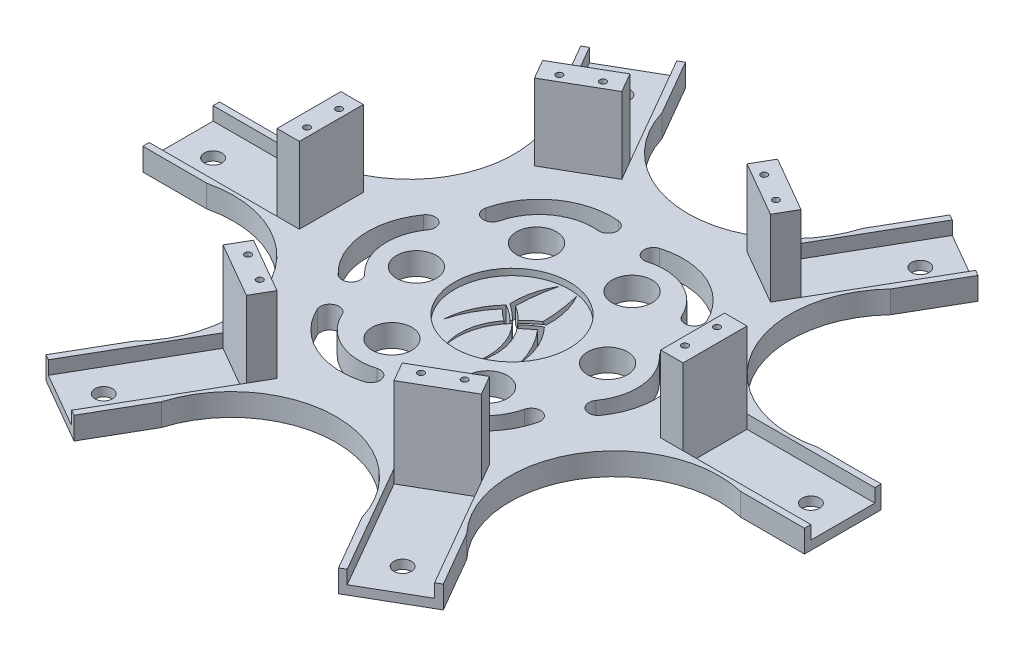
SolidWorks part; units mm, degrees
ref_plane "Front Plane" through (0, 0, 0) normal (0, 0, 1) x (1, 0, 0)
ref_plane "Top Plane" through (0, 0, 0) normal (0, 1, 0) x (1, 0, 0)
ref_plane "Right Plane" through (0, 0, 0) normal (1, 0, 0) x (0, 0, -1)
sketch "Sketch1" plane through (0, 0, 0) normal (0, 1, 0) x (1, 0, 0)
  line L0 (62.1466, -83.641) -> (41.362, -95.641)
  line L7 (103.5085, 12) -> (63.5085, 12)
  line L8 (103.5085, 12) -> (103.5085, -12)
  line L9 (103.5085, -12) -> (63.5085, -12)
  line L10 (63.5085, 12) -> (63.5085, -12)
  line L11 (103.5085, 12) -> (63.5085, -12) construction
  line L12 (103.5085, -12) -> (63.5085, 12) construction
  line L13 (62.1466, -83.641) -> (42.1466, -49)
  line L14 (42.1466, -49) -> (21.362, -61)
  line L15 (41.362, -95.641) -> (21.362, -61)
  line L16 (-41.362, -95.641) -> (-62.1466, -83.641)
  line L17 (-41.362, -95.641) -> (-21.362, -61)
  line L18 (-21.362, -61) -> (-42.1466, -49)
  line L19 (-62.1466, -83.641) -> (-42.1466, -49)
  line L20 (-103.5085, -12) -> (-103.5085, 12)
  line L21 (-103.5085, -12) -> (-63.5085, -12)
  line L22 (-63.5085, -12) -> (-63.5085, 12)
  line L23 (-103.5085, 12) -> (-63.5085, 12)
  line L24 (-62.1466, 83.641) -> (-41.362, 95.641)
  line L25 (-62.1466, 83.641) -> (-42.1466, 49)
  line L26 (-42.1466, 49) -> (-21.362, 61)
  line L27 (-41.362, 95.641) -> (-21.362, 61)
  line L28 (41.362, 95.641) -> (62.1466, 83.641)
  line L29 (41.362, 95.641) -> (21.362, 61)
  line L30 (21.362, 61) -> (42.1466, 49)
  line L31 (62.1466, 83.641) -> (42.1466, 49)
  arc A1 (52.1466, 66.3205) -> (83.5085, 12) centre (75.9923, 43.8742) ccw
  arc A2 (83.5085, -12) -> (52.1466, -66.3205) centre (75.9923, -43.8742) ccw
  arc A3 (31.362, -78.3205) -> (-31.362, -78.3205) centre (0, -87.7484) ccw
  arc A4 (-52.1466, -66.3205) -> (-83.5085, -12) centre (-75.9923, -43.8742) ccw
  arc A5 (-83.5085, 12) -> (-52.1466, 66.3205) centre (-75.9923, 43.8742) ccw
  arc A6 (-31.362, 78.3205) -> (31.362, 78.3205) centre (0, 87.7484) ccw
  point P1 (83.5085, 0)
  point P36 (0, 0)
  point P55 (0, 0)
  dimension "D3" = 24
  dimension "D5" = 40
  dimension "D7" = 6
  dimension "D8" = 6
extrude "Boss-Extrude2" add sketch "Sketch1" along normal blind 10 contours A6 L27 L26 L25 A5 L23 L22 L21 A4 L19 L18 L17 A3 L15 L14 L13 A2 L9 L10 L7 A1 L31 L30 L29 | A6 L27 L24 L25 A5 L26 | A6 L29 L30 L31 A1 L28 | A5 L23 L20 L21 A4 L22 | A4 L19 L16 L17 A3 L18 | A3 L15 L0 L13 A2 L14 | A2 L9 L8 L7 A1 L10 region at (41.8243, 0, 72.4419) region at (0, 0, 0) region at (83.6486, 0, 0) region at (-41.8243, 0, 72.4419) region at (41.8243, 0, -72.4419) region at (-83.6486, 0, 0) region at (-41.8243, 0, -72.4419)
sketch "Sketch2" plane through (0, 0, 0) normal (0, -1, 0) x (1, 0, 0)
  line L0 (103.5085, -12) -> (103.5085, 12) construction
  line L1 (73.5085, 15) -> (103.5085, 15)
  line L2 (73.5085, 15) -> (73.5085, -15)
  line L3 (73.5085, -15) -> (103.5085, -15)
  line L4 (103.5085, 15) -> (103.5085, -15)
  line L5 (73.5085, 15) -> (103.5085, -15) construction
  line L6 (73.5085, -15) -> (103.5085, 15) construction
  point P0 (88.5085, 0)
  dimension "D1" = 30
  dimension "D2" = 30
  dimension "D3" = 0
extrude "Cut-Extrude1" cut sketch "Sketch2" against normal blind 3
sketch "Sketch3" plane through (0, 3, 0) normal (0, -1, 0) x (1, 0, 0)
  line L0 (103.5085, -12) -> (103.5085, 12) construction
  circle A0 centre (93.5085, 0) radius 2.75
  dimension "D1" = 5.5
  dimension "D2" = 10
extrude "Boss-Extrude3" add sketch "Sketch3" along normal blind 3
sketch "Sketch4" plane through (103.5085, 0, 0) normal (1, 0, 0) x (0, 0, -1)
  line L0 (-2.75, 3) -> (2.75, 3) construction
  line L1 (-10, 11.5957) -> (10, 11.5957)
  line L2 (-10, 11.5957) -> (-10, 5.8)
  line L3 (-10, 5.8) -> (10, 5.8)
  line L4 (10, 11.5957) -> (10, 5.8)
  line L5 (-10, 11.5957) -> (10, 5.8) construction
  line L6 (-10, 5.8) -> (10, 11.5957) construction
  point P0 (0, 8.6979)
  dimension "D1" = 20
  dimension "D2" = 2.8
  dimension "D3" = 0
extrude "Cut-Extrude2" cut sketch "Sketch4" against normal blind 40
sketch "Sketch5" plane through (0, 10, 0) normal (0, 1, 0) x (1, 0, 0)
  line L1 (56.5085, 10) -> (63.5085, 10)
  line L2 (56.5085, 10) -> (56.5085, -10)
  line L3 (56.5085, -10) -> (63.5085, -10)
  line L4 (63.5085, 10) -> (63.5085, -10)
  line L5 (56.5085, 10) -> (63.5085, -10) construction
  line L6 (56.5085, -10) -> (63.5085, 10) construction
  circle A0 centre (59.1085, 5) radius 1
  circle A1 centre (59.1085, -5) radius 1
  point P0 (60.0085, 0)
  dimension "D2" = 2
  dimension "D1" = 7
  dimension "D3" = 0
  dimension "D4" = 2.6
  dimension "D5" = 10
  dimension "D6" = 5
extrude "Boss-Extrude5" add sketch "Sketch5" along normal blind 23.8
sketch "Sketch7" plane through (0, 10, 0) normal (0, 1, 0) x (1, 0, 0)
  circle A0 centre (0, 0) radius 17.9565
extrude "Cut-Extrude3" cut sketch "Sketch7" against normal blind 2
pattern_circular "CirPattern1" count 6 over 360 about axis through (0, 10, 0) along (0, 1, 0) of "Cut-Extrude1", "Cut-Extrude2", "Boss-Extrude5", "Boss-Extrude3"
sketch "Sketch9" plane through (0, 10, 0) normal (0, 1, 0) x (1, 0, 0)
  arc A0 (-38.6212, 11.6598) -> (-36.1578, -14.0999) centre (-22.6064, 0.1937) ccw construction
  arc A1 (-40.9975, 13.3612) -> (-38.1686, -16.2209) centre (-22.6064, 0.1937) ccw
  arc A2 (-36.2448, 9.9584) -> (-34.147, -11.979) centre (-22.6064, 0.1937) ccw
  arc A3 (-36.2448, 9.9584) -> (-40.9975, 13.3612) centre (-38.6212, 11.6598) ccw
  arc A4 (-38.1686, -16.2209) -> (-34.147, -11.979) centre (-36.1578, -14.0999) ccw
  point P3 (-42.2133, -1.6813)
extrude "Cut-Extrude4" cut sketch "Sketch9" against normal blind 10 contours A2 A4 A1 A3
pattern_circular "CirPattern2" count 6 over 360 about axis through (0, 8, 0) along (0, 1, 0) of "Cut-Extrude4"
sketch "Sketch10" plane through (0, 10, 0) normal (0, 1, 0) x (1, 0, 0)
  line L0 (-21.862, 32.5703) -> (0, 0) construction
  arc A0 (-9.4982, 36.3682) -> (-27.4476, 23.5827) centre (-11.1355, 19.6746) ccw construction
  circle A1 centre (-15.6448, 23.3079) radius 6.2284
extrude "Cut-Extrude5" cut sketch "Sketch10" against normal blind 10
pattern_circular "CirPattern3" count 6 over 360 about axis through (0, 8, 0) along (0, 1, 0) of "Cut-Extrude5"
sketch "Sketch11" plane through (0, 0, 0) normal (0, -1, 0) x (1, 0, 0)
  circle A0 centre (0, 0) radius 76.7132
extrude "Cut-Extrude6" cut sketch "Sketch11" against normal up to surface (3 mm away) up to face at (-44.3727, 3, 82.3558)
extrude "Cut-Extrude14" cut sketch "Sketch3<3>" against normal blind 10 and the other way blind 10
sketch "Sketch3<3>" plane through (0, 3, 0) normal (0, -1, 0) x (1, 0, 0) same geometry as "Sketch3"
pattern_circular "CirPattern4" count 6 over 360 about axis through (0, 10, 0) along (0, 1, 0) of "Cut-Extrude14"
sketch "Sketch12" plane through (0, 8, 0) normal (0, 1, 0) x (1, 0, 0)
  line L0 (0.3324, 1.5322) -> (0.3324, -0.2611) construction
  line L1 (-0.4865, 0.5803) -> (-0.8682, 0.2689)
  line L2 (1.1513, 0.5803) -> (1.533, 0.2689)
  arc A0 (0.3324, 1.5322) -> (-3.9728, 5.0753) centre (-15.1626, -12.9085) ccw
  arc A1 (-3.9728, 5.0753) -> (-2.3827, 17.1722) centre (52.8389, 3.7605) cw
  arc A2 (-2.3827, 17.1722) -> (-5.4009, 4.7452) centre (16.843, 5.9228) ccw
  arc A3 (-5.4009, 4.7452) -> (-0.4865, 0.5803) centre (-21.1165, -18.7803) cw
  arc A4 (-0.8682, 0.2689) -> (-5.6399, 3.825) centre (-16.156, -15.265) ccw
  arc A5 (-5.6399, 3.825) -> (-11.6079, -9.8616) centre (10.1529, -11.2059) ccw
  arc A6 (-11.6079, -9.8616) -> (-5.2005, 2.161) centre (16.4207, -17.0808) cw
  arc A7 (-5.2005, 2.161) -> (-1.702, -0.7521) centre (8.1199, 14.6005) ccw
  arc A8 (-1.702, -0.7521) -> (-4.1758, -16.9137) centre (10.9658, -10.9613) ccw
  arc A9 (-4.1758, -16.9137) -> (0.3324, -0.2611) centre (13.6032, -12.7904) cw
  arc A10 (4.8406, -16.9137) -> (0.3324, -0.2611) centre (-12.9384, -12.7904) ccw
  arc A11 (2.3669, -0.7521) -> (4.8406, -16.9137) centre (-10.301, -10.9613) cw
  arc A12 (6.3047, 3.825) -> (12.2727, -9.8616) centre (-9.488, -11.2059) cw
  arc A13 (12.2727, -9.8616) -> (5.8653, 2.161) centre (-15.7559, -17.0808) ccw
  arc A14 (5.8653, 2.161) -> (2.3669, -0.7521) centre (-7.4551, 14.6005) cw
  arc A15 (1.533, 0.2689) -> (6.3047, 3.825) centre (16.8208, -15.265) cw
  arc A16 (6.0657, 4.7452) -> (1.1513, 0.5803) centre (21.7813, -18.7803) ccw
  arc A17 (0.3324, 1.5322) -> (4.6376, 5.0753) centre (15.8275, -12.9085) cw
  arc A18 (3.0475, 17.1722) -> (6.0657, 4.7452) centre (-16.1782, 5.9228) cw
  arc A19 (4.6376, 5.0753) -> (3.0475, 17.1722) centre (-52.1741, 3.7605) ccw
extrude "Cut-Extrude15" cut sketch "Sketch12" against normal blind 10 contours A10 A9 A8 A7 A6 A5 A4 L1 A3 A2 A1 A0 A17 A19 A18 A16 L2 A15 A12 A13 A14 A11
